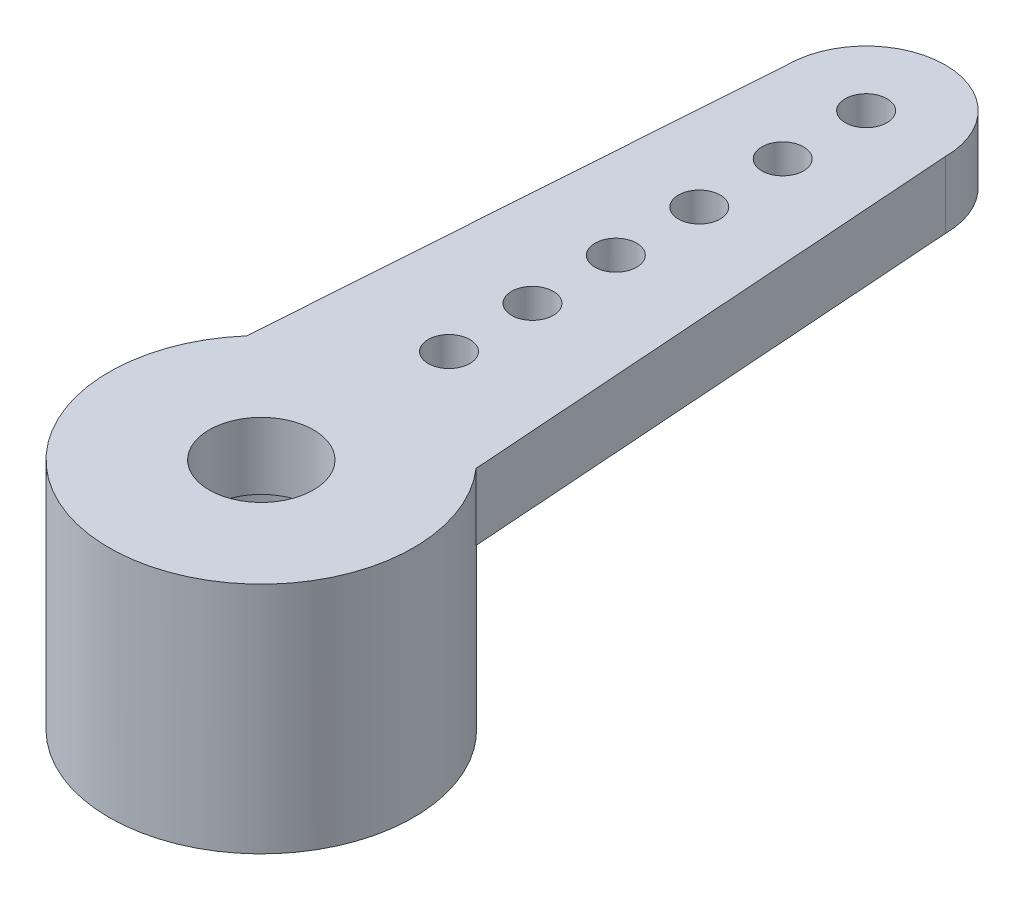
SolidWorks part; units mm, degrees
ref_plane "Front Plane" through (0, 0, 0) normal (0, 0, 1) x (1, 0, 0)
ref_plane "Top Plane" through (0, 0, 0) normal (0, 1, 0) x (1, 0, 0)
ref_plane "Right Plane" through (0, 0, 0) normal (1, 0, 0) x (0, 0, -1)
sketch "Sketch1" plane through (0, 0, 0) normal (0, 1, 0) x (1, 0, 0)
  circle A0 centre (0, 0) radius 2.5
  circle A1 centre (0, 0) radius 3.65
  dimension "D1" = 5
  dimension "D2" = 7.3
extrude "Boss-Extrude1" add sketch "Sketch1" along normal blind 4
sketch "Sketch2" plane through (0, 4, 0) normal (0, 1, 0) x (1, 0, 0)
  line L0 (0, 0) -> (0, 14.5) construction
  line L10 (-2.75, 2.4) -> (-1.9, 14.5)
  line L11 (1.9, 14.5) -> (2.75, 2.4)
  circle A5 centre (0, 0) radius 1.25
  circle A6 centre (0, 0) radius 3.65 construction
  arc A7 (-2.75, 2.4) -> (2.75, 2.4) centre (0, 0) ccw
  arc A8 (-1.9, 14.5) -> (1.9, 14.5) centre (0, 14.5) cw
  point P6 (0, 0)
  point P9 (0, 0)
  dimension "D1" = 2.5
  dimension "D4" = 5.5
  dimension "D3" = 1.9
  dimension "D2" = 14.5
extrude "Boss-Extrude2" add sketch "Sketch2" along normal blind 1.6
sketch "Sketch3" plane through (0, 5.6, 0) normal (0, 1, 0) x (1, 0, 0)
  line L0 (0, 0) -> (0, 14.5) construction
  circle A0 centre (0, 12.5) radius 0.5
  circle A1 centre (0, 10.5) radius 0.5
  circle A2 centre (0, 14.5) radius 0.5
  circle A4 centre (0, 8.5) radius 0.5
  circle A5 centre (0, 6.5) radius 0.5
  circle A6 centre (0, 4.5) radius 0.5
  point P8 (0, 0)
  point P15 (0, 0)
  dimension "D3" = 1
extrude "Cut-Extrude1" cut sketch "Sketch3" against normal up to next
